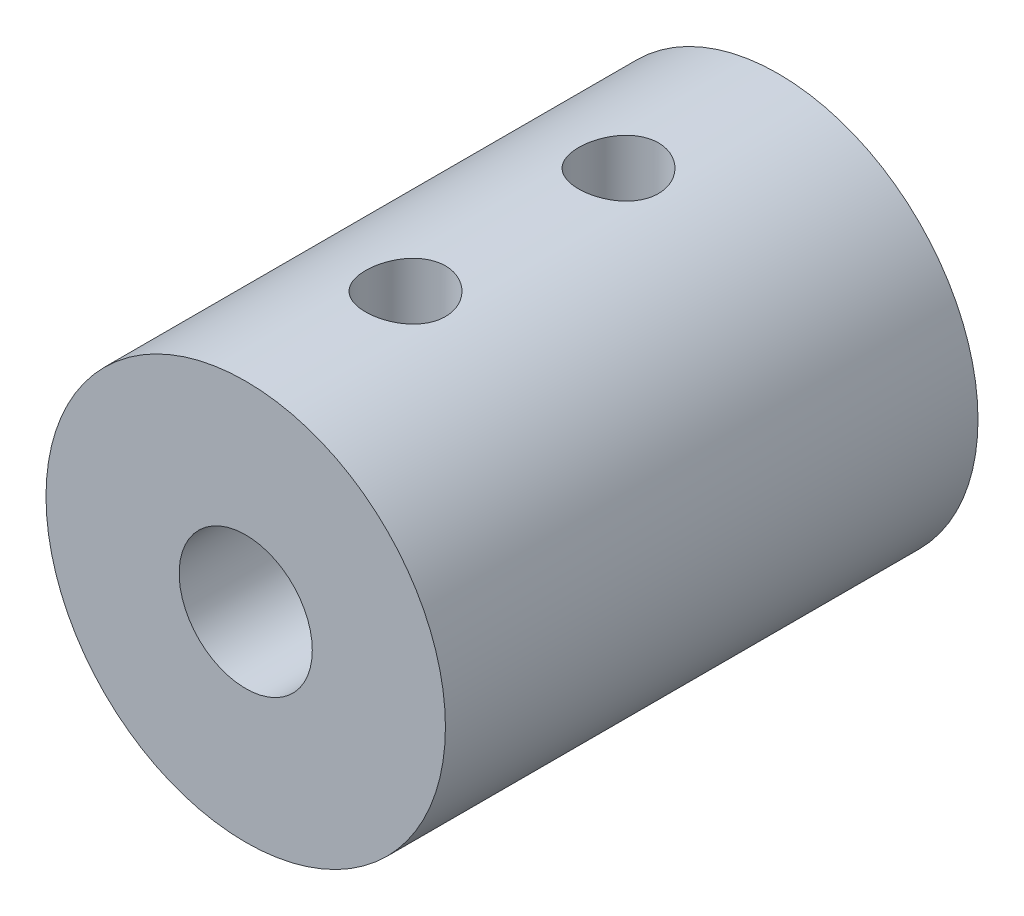
SolidWorks part; units mm, degrees
ref_plane "Спереди" through (0, 0, 0) normal (0, 0, 1) x (1, 0, 0)
ref_plane "Сверху" through (0, 0, 0) normal (0, 1, 0) x (1, 0, 0)
ref_plane "Справа" through (0, 0, 0) normal (1, 0, 0) x (0, 0, -1)
sketch "Эскиз1" plane through (0, 0, 0) normal (0, 0, 1) x (1, 0, 0)
  circle A0 centre (0, 0) radius 2.5
  circle A1 centre (0, 0) radius 7.5
  dimension "D1" = 5
  dimension "D2" = 15
extrude "Бобышка-Вытянуть1" add sketch "Эскиз1" along normal blind 20
sketch "Эскиз2" plane through (0, 0, 0) normal (0, 1, 0) x (1, 0, 0)
  line L0 (0, -1000) -> (0, 49000) construction
  line L1 (-1000, -6) -> (49000, -6) construction
  line L2 (-1000, -14) -> (49000, -14) construction
  line L3 (7.5, 0) -> (-7.5, 0) construction
  line L4 (-7.5, -20) -> (7.5, -20) construction
  circle A0 centre (0, -6) radius 1.5
  circle A1 centre (0, -14) radius 1.5
  dimension "D3" = 3
  dimension "D4" = 3
  dimension "D1" = 6
  dimension "D2" = 6
extrude "Вырез-Вытянуть1" cut sketch "Эскиз2" against normal blind 20 and the other way blind 20
